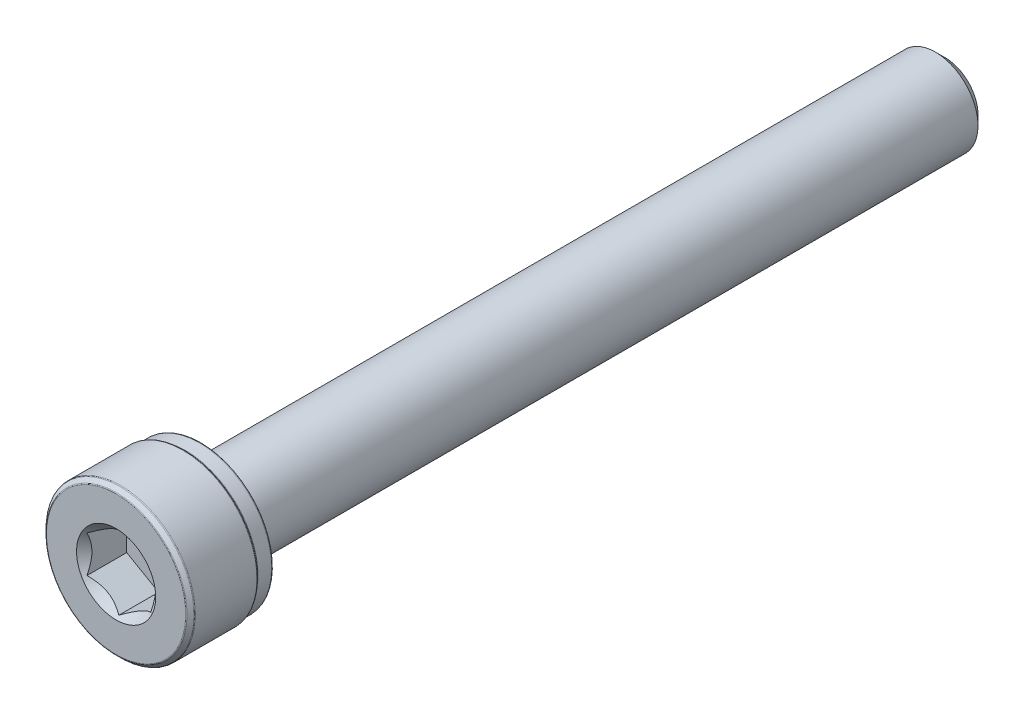
SolidWorks part; units mm, degrees
material "Alloy Steel"
ref_plane "Front Plane" through (0, 0, 0) normal (0, 0, 1) x (1, 0, 0)
ref_plane "Top Plane" through (0, 0, 0) normal (0, 1, 0) x (1, 0, 0)
ref_plane "Right Plane" through (0, 0, 0) normal (1, 0, 0) x (0, 0, -1)
sketch "Sketch1" plane through (0, 0, 0) normal (1, 0, 0) x (0, 0, -1)
  line L0 (-19.5, 0) -> (19.5, 0) construction
  line L1 (19.5, 0) -> (19.5, 1.5453) construction
  line L2 (19.5, 1.5453) -> (19.0453, 2) construction
  line L3 (19.0453, 2) -> (18.975, 2) construction
  line L4 (18.975, 2) -> (-15.5, 2) construction
  line L5 (-15.5, 2) -> (-15.5, 3.5) construction
  line L6 (-15.5, 3.5) -> (-19.5, 3.5) construction
  line L7 (-19.5, 3.5) -> (-19.5, 0) construction
  line L8 (19.5, 1.5453) -> (19.5, 2) construction
  line L9 (19.4563, 2.0758) -> (19.8063, 1.4696) construction
  line L10 (19.8063, 1.4696) -> (20.1563, 2.0758) construction
  line L11 (20.1563, 2.0758) -> (19.4563, 2.0758) construction
  line L12 (19.8063, 2.0758) -> (19.8063, 2) construction
  line L13 (19.8063, 1.4696) -> (19.8063, 1.5453) construction
  line L14 (19.7625, 1.5453) -> (19.85, 1.5453) construction
  line L15 (19.5, 2) -> (20.1125, 2) construction
  line L16 (19.4781, 2.0379) -> (20.1344, 2.0379) construction
  line L17 (19.5, 0) -> (19.5, -2) construction
  line L18 (-15.7, 3.5) -> (-15.5, 3.3) construction
  line L19 (-19.3, 3.5) -> (-19.5, 3.3) construction
  line L20 (-15.5, 2) -> (-15.5, 0) construction
  line L21 (-15.5, 1) -> (-3.8333, 1) construction
  line L22 (-3.8333, 1) -> (7.8333, 1) construction
  line L23 (7.8333, 1) -> (19.5, 1) construction
  line L24 (-3.8333, 1) -> (-3.8333, 2) construction
  line L25 (-3.8333, 2) -> (-3.8333, 3.5) construction
  line L26 (7.8333, 1) -> (7.8333, 3.5) construction
  point P0 (-19.5, 1.5)
  point P3 (17.75, 2)
  point P4 (0, 0)
  point P18 (7.8333, 2)
  point P22 (19.8063, 1.5453)
  point P24 (18.975, 2)
  point P25 (19.8063, 2)
  point P28 (19.8063, 2.0379)
  point P29 (17.75, -2)
  point P30 (-3.8333, 2)
  point P31 (-17.5, 3.5)
  point P37 (-16.2, 3.5)
  point P38 (-19.2, 3.5)
  point P45 (-3.8333, 1)
  point P46 (7.8333, 1)
  dimension "D1" = 45
  dimension "D2" = 0.0875
  dimension "D7" = 0.2
  dimension "D8" = 0.2
  dimension "D9" = 0.2
  dimension "D10" = 0.1
  dimension "D11" = 0.5
  dimension "Drive Size" = 3
  dimension "Head Diameter" = 7
  dimension "Head Height" = 4
  dimension "Thread Pitch" = 0.7
  dimension "Thread Dia" = 4
  dimension "Length" = 35
  dimension "D12" = 0.525
  dimension "D4" = 1.75
  dimension "Key Engagement" = 2
sketch "Sketch2" plane through (0, 0, 0) normal (1, 0, 0) x (0, 0, -1)
  line L0 (-19.5, 0) -> (-19.5, 3.2741)
  line L1 (-19.2741, 3.5) -> (-16.3759, 3.5)
  line L2 (-15.5, 3.3125) -> (-15.5, 2.2)
  line L4 (19.0453, 2) -> (19.5, 1.5453)
  line L5 (19.5, 1.5453) -> (19.5, 0)
  line L6 (-15.5, 3.5) -> (-19.5, 3.5) construction
  line L7 (19.5, 0) -> (-19.5, 0)
  line L8 (-19.3, 3.5) -> (-19.5, 3.3) construction
  line L10 (-19.3183, 3.4817) -> (-19.4817, 3.3183)
  line L12 (-16.2241, 3.4) -> (-15.5875, 3.4)
  line L14 (-15.7, 3.5) -> (-15.5, 3.3) construction
  line L15 (-16.3317, 3.4817) -> (-16.2683, 3.4183)
  line L17 (-15.5, 2) -> (-15.5, 3.5) construction
  line L19 (-15.3, 2) -> (19.0453, 2)
  line L20 (18.975, 2) -> (-15.5, 2) construction
  arc A0 (-15.5875, 3.4) -> (-15.5, 3.3125) centre (-15.5875, 3.3125) cw
  arc A1 (-15.5, 2.2) -> (-15.3, 2) centre (-15.3, 2.2) ccw
  arc A2 (-19.3183, 3.4817) -> (-19.2741, 3.5) centre (-19.2741, 3.4375) cw
  arc A3 (-19.4817, 3.3183) -> (-19.5, 3.2741) centre (-19.4375, 3.2741) ccw
  arc A4 (-16.3317, 3.4817) -> (-16.3759, 3.5) centre (-16.3759, 3.4375) ccw
  arc A5 (-16.2683, 3.4183) -> (-16.2241, 3.4) centre (-16.2241, 3.4625) ccw
  point P22 (-15.6, 3.4)
  point P37 (-16.25, 3.4)
  dimension "D2" = 0.0875
  dimension "D3" = 0.2
  dimension "D4" = 0.0625
  dimension "D1" = 0.75
revolve "Revolve1" add sketch "Sketch2" angle 360 about L7
sketch "Sketch3" plane through (0, 0, 19.5) normal (0, 0, 1) x (1, 0, 0)
  line L1 (1.5, -0.866) -> (1.5, 0.866)
  line L2 (1.5, 0.866) -> (0, 1.7321)
  line L3 (0, 1.7321) -> (-1.5, 0.866)
  line L4 (-1.5, 0.866) -> (-1.5, -0.866)
  line L5 (-1.5, -0.866) -> (0, -1.7321)
  line L6 (0, -1.7321) -> (1.5, -0.866)
  circle A0 centre (0, 0) radius 1.5 construction
  circle A1 centre (0, 0) radius 3.5 construction
  circle A2 centre (0, 0) radius 3.5 construction
  circle A3 centre (0, 0) radius 1.7321 construction
  dimension "D1" = 3.4641
extrude "Cut-Extrude1" cut sketch "Sketch3" against normal up to vertex (2 mm away) up to point (0, 3.5, 17.5)
sketch "Sketch4" plane through (0, 0, 19.5) normal (0, 0, 1) x (1, 0, 0)
  circle A0 centre (0, 0) radius 1.862
  dimension "D1" = 3.7239
extrude "Cut-Extrude2" cut sketch "Sketch4" against normal up to vertex (2 mm away) draft 45 up to point (0, 3.5, 17.5)
sketch "Sketch6" [suppressed] plane through (0, 0, -19.5) normal (0, 0, -1) x (-1, 0, 0)
  circle A0 centre (0, 0) radius 2
curve "Helix/Spiral1" [suppressed] pitch 0.7 height 35.7 turns 51
sketch "Sketch7" [suppressed] plane through (0, 0, 0) normal (1, 0, 0) x (0, 0, -1)
  line L0 (19.4781, 2.0379) -> (20.1344, 2.0379)
  line L1 (20.1344, 2.0379) -> (19.85, 1.5453)
  line L2 (19.85, 1.5453) -> (19.7625, 1.5453)
  line L3 (19.7625, 1.5453) -> (19.4781, 2.0379)
sweep "Cut-Sweep1" [suppressed] cut profiles "Sketch7" path "Helix/Spiral1"
sketch "Sketch8" [suppressed] plane through (0, 0, 0) normal (1, 0, 0) x (0, 0, -1)
  line L0 (-17.5, 0) -> (-17.5, 2.2)
  line L1 (-17.5, 0.866) -> (-17.5, 1.7321) construction
  line L2 (-15.3, 2) -> (-15.15, 2)
  line L3 (-15.5, 2.2) -> (-17.5, 2.2)
  line L4 (-15.15, 2) -> (-13.9953, 0)
  line L5 (-13.9953, 0) -> (-17.5, 0)
  line L7 (-19.5, 0) -> (19.5, 0) construction
  line L8 (-15.5, 2) -> (-15.5, 3.5) construction
  arc A0 (-15.5, 2.2) -> (-15.3, 2) centre (-15.3, 2.2) ccw construction
  arc A1 (-15.5, 2.2) -> (-15.3, 2) centre (-15.3, 2.2) ccw
  dimension "D1" = 60
  dimension "D2" = 0.35
revolve "Revolve2" [suppressed] add sketch "Sketch8" angle 360 about L5
sketch "Sketch9" [suppressed] plane through (0, 0, 19.5) normal (0, 0, 1) x (1, 0, 0)
  line L0 (-0.016, 3.4357) -> (-0.0875, 3.5954)
  line L1 (-0.0875, 3.5954) -> (0.0875, 3.5954)
  line L2 (0.0875, 3.5954) -> (0.016, 3.4357)
  line L3 (0, 3.5) -> (0, 3.3) construction
  line L4 (0, 0) -> (-0.0875, 3.5954) construction
  line L5 (0.0875, 3.5954) -> (0, 0) construction
  circle A0 centre (0, 0) radius 3.4 construction
  arc A4 (-0.016, 3.4357) -> (0.016, 3.4357) centre (0, 3.4428) ccw
  point P10 (0, 3.4)
  point P19 (0, 3.4)
  dimension "D2" = 0.0175
  dimension "D1" = 0.175
  dimension "D3" = 2.788
extrude "Cut-Extrude3" [suppressed] cut sketch "Sketch9" against normal through all
pattern_circular "CirPattern1" [suppressed] count 80 over 360 of bodies 112
equation "\"D2@Sketch1\" = \"Thread Pitch@Sketch1\" / 8"
equation "\"D4@Helix/Spiral1\" = \"Thread Pitch@Sketch1\""
equation "\"D7@Sketch1\" = \"Head Height@Sketch1\" * .05"
equation "\"D8@Sketch1\"=\"D7@Sketch1\""
equation "\"D9@Sketch1\"=\"D7@Sketch1\""
equation "\"D10@Sketch1\"=\"D7@Sketch1\"/2"
equation "\"D11@Sketch1\"=\"D10@Sketch1\"*5"
equation "\"D4@Sketch1\"=\"Thread Pitch@Sketch1\"*2.5"
equation "\"D12@Sketch1\"=\"Thread Pitch@Sketch1\"*.75"
equation "\"D3@Helix/Spiral1\"=\"Length@Sketch1\"+\"Thread Pitch@Sketch1\""
equation "\"D1@Sketch2\"=\"Head Height@Sketch1\"*0.1875"
equation "\"D2@Sketch2\"=\"Head Diameter@Sketch1\"*0.0125"
equation "\"D3@Sketch2\"=\"Thread Dia@Sketch1\"*0.05"
equation "\"D1@Sketch9\"=\"Head Diameter@Sketch1\"*0.025"
equation "\"D2@Sketch9\"=\"D1@Sketch9\"*0.1"
equation "\"D2@Sketch8\"=\"Thread Pitch@Sketch1\"*00.5"
equation "\"D4@Sketch2\"=\"D8@Sketch1\"*0.3125"
equation "\"D1@CirPattern1\"=int ((360/\"D3@Sketch9\")*0.625)"
equation "\"D1@Sketch4\"=\"D1@Sketch3\" * 01.075"
